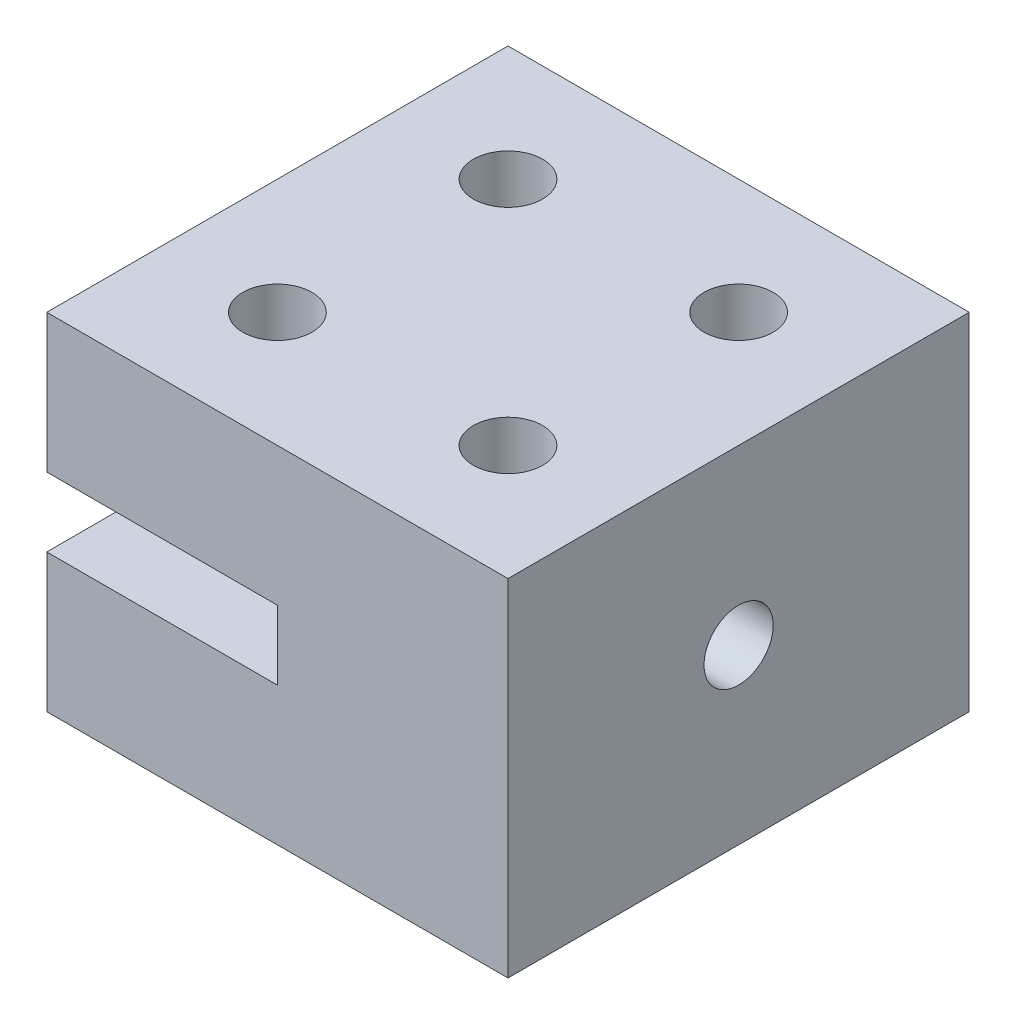
SolidWorks part; units mm, degrees
ref_plane "Front Plane" through (0, 0, 0) normal (0, 0, 1) x (1, 0, 0)
ref_plane "Top Plane" through (0, 0, 0) normal (0, 1, 0) x (1, 0, 0)
ref_plane "Right Plane" through (0, 0, 0) normal (1, 0, 0) x (0, 0, -1)
sketch "Sketch1" plane through (0, 0, 0) normal (0, 1, 0) x (1, 0, 0)
  line L5 (-10, 10) -> (10, 10)
  line L6 (-10, 10) -> (-10, -10)
  line L7 (-10, -10) -> (10, -10)
  line L8 (10, 10) -> (10, -10)
  line L9 (-10, 10) -> (10, -10) construction
  line L10 (-10, -10) -> (10, 10) construction
  point P1 (0, 0)
  dimension "D1" = 20
  dimension "D2" = 20
extrude "Boss-Extrude1" add sketch "Sketch1" along normal mid plane 15
extrude "Cut-Extrude2" cut sketch "Sketch1<3>" against normal mid plane 3
sketch "Sketch1<3>" plane through (0, 0, 0) normal (0, 1, 0) x (1, 0, 0) same geometry as "Sketch1"
sketch "Sketch3" plane through (0, 0, 0) normal (0, 1, 0) x (1, 0, 0)
  line L0 (10, 10) -> (-10, 10) construction
  line L1 (0, 10) -> (10, 10)
  line L2 (0, 10) -> (0, -10)
  line L3 (0, -10) -> (10, -10)
  line L4 (10, 10) -> (10, -10)
extrude "Boss-Extrude2" add sketch "Sketch3" along normal mid plane 3
sketch "Sketch4" plane through (10, 0, 0) normal (1, 0, 0) x (0, 0, -1)
  circle A0 centre (0, 0) radius 1.5
  dimension "D1" = 3
extrude "Cut-Extrude3" cut sketch "Sketch4" against normal blind 5
sketch "Sketch5" plane through (0, 0, 0) normal (0, 1, 0) x (1, 0, 0)
  line L1 (-5, 5) -> (5, 5) construction
  line L2 (-5, 5) -> (-5, -5) construction
  line L3 (-5, -5) -> (5, -5) construction
  line L4 (5, 5) -> (5, -5) construction
  line L5 (-5, 5) -> (5, -5) construction
  line L6 (-5, -5) -> (5, 5) construction
  circle A0 centre (-5, 5) radius 1.5
  circle A1 centre (5, 5) radius 1.5
  circle A2 centre (5, -5) radius 1.5
  circle A3 centre (-5, -5) radius 1.5
  point P0 (0, 0)
  dimension "D3" = 3
  dimension "D1" = 10
  dimension "D2" = 10
extrude "mounthole" cut sketch "Sketch5" against normal through all both and the other way through all
fillet "Fillet1" [suppressed] radius 1
ref_plane "Plane1" through (5, 0, 0) normal (1, 0, 0) x (0, 0, -1)
sketch "Sketch6" plane through (5, 0, 0) normal (1, 0, 0) x (0, 0, -1)
  circle A0 centre (0, 0) radius 3
  dimension "D1" = 6
extrude "Cut-Extrude5" cut sketch "Sketch6" against normal mid plane 2.5
